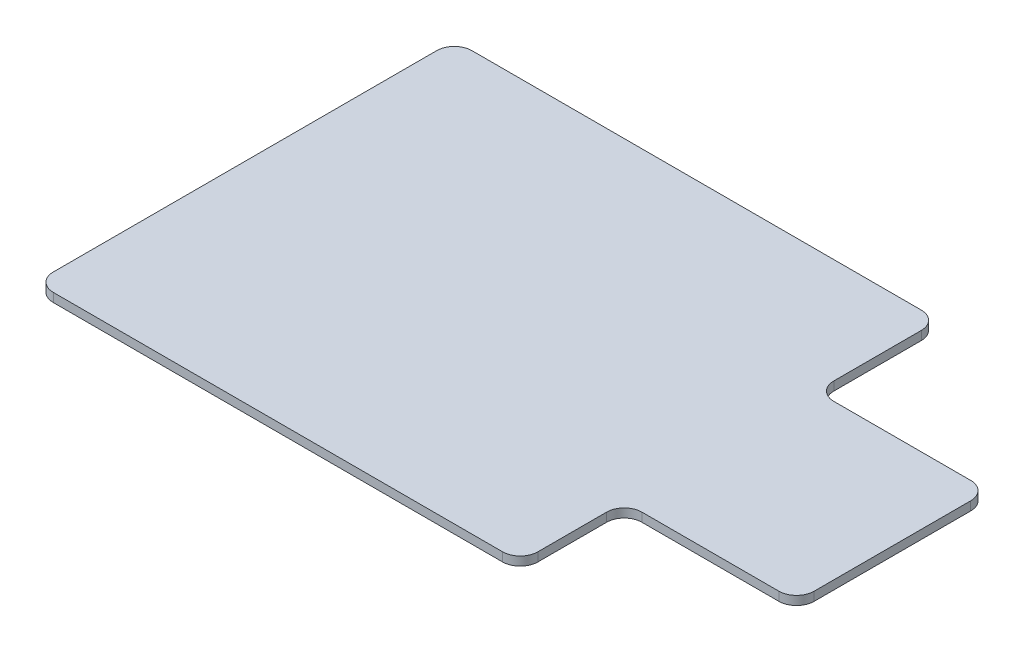
SolidWorks part; units mm, degrees
ref_plane "Front Plane" through (0, 0, 0) normal (0, 0, 1) x (1, 0, 0)
ref_plane "Top Plane" through (0, 0, 0) normal (0, 1, 0) x (1, 0, 0)
ref_plane "Right Plane" through (0, 0, 0) normal (1, 0, 0) x (0, 0, -1)
sketch "Sketch1" plane through (0, 0, 0) normal (0, 1, 0) x (1, 0, 0)
  line L0 (69.7929, 30.0104) -> (69.7929, 55.2197)
  line L1 (-64.7129, -60.2997) -> (64.7129, -60.2997)
  line L2 (-69.7929, -55.2197) -> (-69.7929, 55.2197)
  line L3 (-64.7129, 60.2997) -> (64.7129, 60.2997)
  line L4 (69.7929, -55.2197) -> (69.7929, -35.4141)
  line L5 (-69.7929, -60.2997) -> (69.7929, 60.2997) construction
  line L6 (-69.7929, 60.2997) -> (69.7929, -60.2997) construction
  line L7 (74.8729, 24.9304) -> (114.3282, 24.9304)
  line L9 (74.8729, -30.3341) -> (114.3282, -30.3341)
  line L10 (119.4082, 19.8504) -> (119.4082, -25.2541)
  arc A0 (-64.7129, -60.2997) -> (-69.7929, -55.2197) centre (-64.7129, -55.2197) cw
  arc A1 (-69.7929, 55.2197) -> (-64.7129, 60.2997) centre (-64.7129, 55.2197) cw
  arc A2 (64.7129, -60.2997) -> (69.7929, -55.2197) centre (64.7129, -55.2197) ccw
  arc A3 (114.3282, -30.3341) -> (119.4082, -25.2541) centre (114.3282, -25.2541) ccw
  arc A4 (114.3282, 24.9304) -> (119.4082, 19.8504) centre (114.3282, 19.8504) cw
  arc A5 (64.7129, 60.2997) -> (69.7929, 55.2197) centre (64.7129, 55.2197) cw
  arc A6 (69.7929, -35.4141) -> (74.8729, -30.3341) centre (74.8729, -35.4141) cw
  arc A7 (74.8729, 24.9304) -> (69.7929, 30.0104) centre (74.8729, 30.0104) cw
  point P0 (0, 0)
  point P30 (69.7929, 24.9304)
  dimension "D1" = 5.08
  dimension "D2" = 5.08
extrude "Boss-Extrude1" add sketch "Sketch1" along normal blind 2.54 contours L1 L4 L3 L2 | L10 L7 L4 L9 region at (13.2387, 0, 0.3789)
